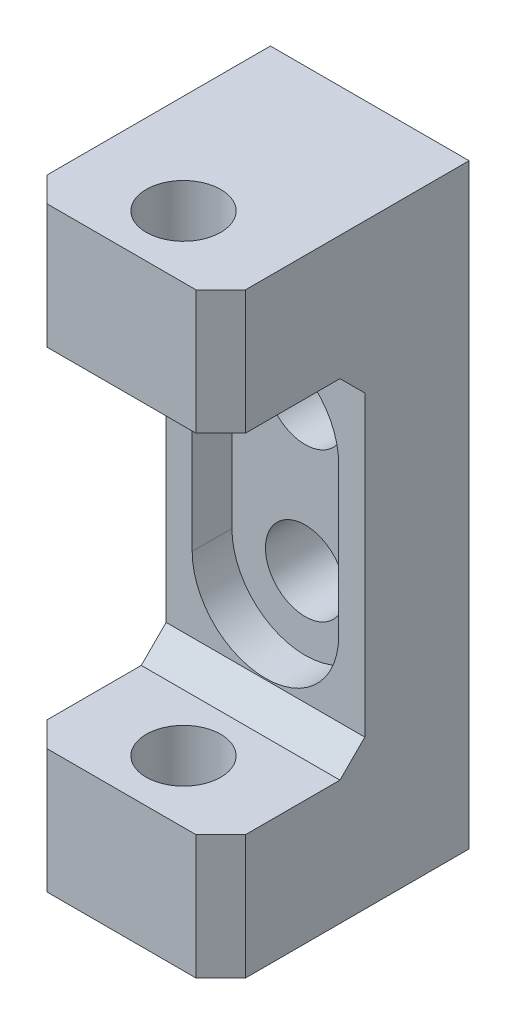
SolidWorks part; units mm, degrees
ref_plane "前视基准面" through (0, 0, 0) normal (0, 0, 1) x (1, 0, 0)
ref_plane "上视基准面" through (0, 0, 0) normal (0, 1, 0) x (1, 0, 0)
ref_plane "右视基准面" through (0, 0, 0) normal (1, 0, 0) x (0, 0, -1)
sketch "草图2" plane through (0, 0, 0) normal (0, 0, 1) x (1, 0, 0)
  line L0 (72, 105) -> (127, 105) construction
  line L1 (101, 105) -> (93, 105)
  line L2 (101, 105) -> (101, 81)
  line L3 (101, 81) -> (93, 81)
  line L4 (93, 105) -> (93, 81)
  line L6 (97, 81) -> (97, 105) construction
  line L7 (127, 105) -> (127, -105) construction
  dimension "D1" = 24
  dimension "D2" = 8
  dimension "D3" = 30
extrude "凸台-拉伸1" add sketch "草图2" along normal blind 10
sketch "草图3" plane through (93, 0, 0) normal (-1, 0, 0) x (0, 0, 1)
  line L0 (0, 93) -> (22.6575, 93) construction
  line L5 (0, 105) -> (0, 81) construction
  line L6 (10, 81) -> (0, 81) construction
  line L7 (4.2, 100) -> (13.3805, 100)
  line L8 (4.2, 100) -> (4.2, 86)
  line L9 (4.2, 86) -> (13.3805, 86)
  line L10 (13.3805, 100) -> (13.3805, 86)
  line L11 (4.2, 100) -> (13.3805, 86) construction
  line L12 (4.2, 86) -> (13.3805, 100) construction
  point P0 (8.7902, 93)
  dimension "D1" = 4.2
  dimension "D2" = 5
extrude "切除-拉伸1" cut sketch "草图3" against normal blind 40
sketch "草图4" plane through (0, 0, 4.2) normal (0, 0, 1) x (1, 0, 0)
  line L0 (97, 100) -> (97, 86) construction
  line L1 (101, 100) -> (93, 100) construction
  line L2 (101, 86) -> (93, 86) construction
  line L3 (97, 93) -> (101, 93) construction
  line L4 (101, 100) -> (101, 86) construction
  circle A0 centre (97, 96) radius 2
  circle A1 centre (97, 90) radius 2
  dimension "D1" = 4
  dimension "D2" = 6
chamfer "倒角1" distance 1 angle 45 2 edges at (97, 86, 4.2) (97, 100, 4.2)
sketch "草图6" plane through (0, 105, 0) normal (0, 1, 0) x (1, 0, 0)
  line L0 (97, -5.2) -> (97, -10) construction
  line L4 (101, -10) -> (101, -5.2)
  line L5 (101, -5.2) -> (93, -5.2)
  line L6 (93, -5.2) -> (93, -10)
  line L7 (93, -10) -> (101, -10)
  line L8 (101, -10) -> (101, -5.2) construction
  line L9 (101, -5.2) -> (93, -5.2) construction
  line L10 (93, -5.2) -> (93, -10) construction
  line L11 (93, -10) -> (101, -10) construction
  circle A1 centre (97, -7.5) radius 1.5
  dimension "D2" = 3
  dimension "D3" = 2.5
  dimension "D1" = 0
hole_wizard "M3 六角头螺栓的柱形沉头孔1" positions "草图7" profile "草图8" counterbore size "M3" standard "GB" end condition through all
sketch "草图7" plane through (124.3639, -131.0101, 4.2) normal (0, 0, 1) x (0, 1, 0)
  point P0 (221.0101, 27.3639)
  point P3 (227.0101, 27.3639)
sketch "草图8" plane through (97, 90, 4.2) normal (1, 0, 0) x (0, -1, 0)
  line L0 (0, 0) -> (0, 4.2)
  line L1 (0, 4.2) -> (1.6, 4.2)
  line L2 (1.6, 4.2) -> (1.6, 1.6)
  line L3 (1.6, 1.6) -> (2.95, 1.6)
  line L4 (2.95, 1.6) -> (2.95, 0)
  line L5 (2.95, 0) -> (0, 0)
  line L6 (0, -6.35) -> (0, 107.95) construction
  dimension "通孔孔直径" = 3.2
  dimension "通孔孔深度" = 4.2
  dimension "柱形沉头孔直径" = 5.9
  dimension "柱形沉头孔深度" = 1.6
sketch "草图11" plane through (0, 0, 4.2) normal (0, 0, 1) x (1, 0, 0)
  line L0 (97, 90) -> (97, 96) construction
  line L1 (94.05, 90) -> (94.05, 96)
  line L2 (99.95, 90) -> (99.95, 96)
  arc A0 (94.05, 90) -> (99.95, 90) centre (97, 90) ccw
  arc A1 (99.95, 96) -> (94.05, 96) centre (97, 96) ccw
  point P2 (97, 93)
  dimension "D1" = 5.9
extrude "切除-拉伸2" cut sketch "草图11" against normal up to surface (1.6 mm away) up to face at (98.6, 90, 2.6)
hole_wizard "大小mm 暗销孔2" positions "草图12" profile "草图13" hole size "Ø3.0" standard "GB"
sketch "草图12" plane through (124.3639, 105, -5) normal (0, 1, 0) x (-1, 0, 0)
  point P0 (27.3639, 12.5)
sketch "草图13" plane through (97, 105, 7.5) normal (1, 0, 0) x (0, 0, 1)
  line L0 (0, 0) -> (0, 24.9013)
  line L1 (0, 24.9013) -> (1.5, 24)
  line L2 (1.5, 24) -> (1.5, 0)
  line L3 (1.5, 0) -> (0, 0)
  line L4 (0, 24.9013) -> (-1.5, 24) construction
  line L5 (0, -6.35) -> (0, 107.95) construction
  dimension "孔直径" = 3
  dimension "孔深度" = 24
  dimension "导头角度" = 118
chamfer "倒角2" distance 1 angle 45 4 edges at (93, 83.5, 10) (101, 83.5, 10) (101, 102.5, 10) (93, 102.5, 10)
